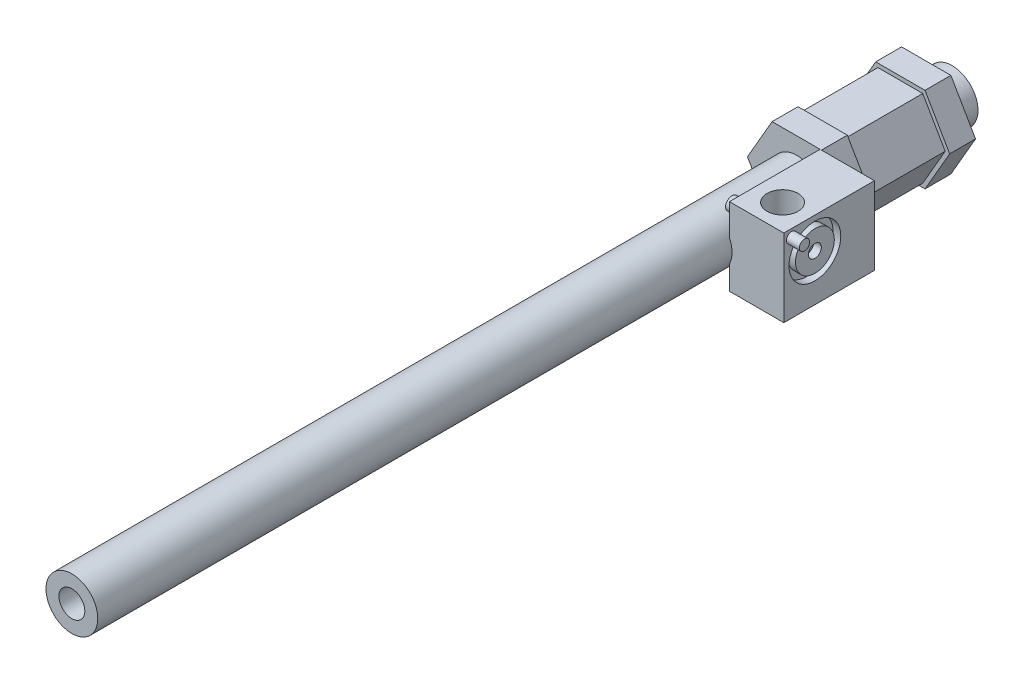
SolidWorks part; units mm, degrees
ref_plane "Front Plane" through (0, 0, 0) normal (0, 0, 1) x (1, 0, 0)
ref_plane "Top Plane" through (0, 0, 0) normal (0, 1, 0) x (1, 0, 0)
ref_plane "Right Plane" through (0, 0, 0) normal (1, 0, 0) x (0, 0, -1)
sketch "Sketch1" plane through (0, 0, 0) normal (0, 0, 1) x (1, 0, 0)
  circle A0 centre (0, 0) radius 10
  dimension "D1" = 20
extrude "Boss-Extrude1" add sketch "Sketch1" along normal blind 340
sketch "Sketch2" plane through (0, 0, 340) normal (0, 0, 1) x (1, 0, 0)
  circle A0 centre (0, 0) radius 5
  dimension "D1" = 10
extrude "Cut-Extrude1" cut sketch "Sketch2" against normal blind 330
sketch "Sketch3" plane through (0, 0, 0) normal (0, 0, -1) x (-1, 0, 0)
  line L1 (17.3205, 0) -> (8.6603, 15)
  line L2 (8.6603, 15) -> (-8.6603, 15)
  line L3 (-8.6603, 15) -> (-17.3205, 0)
  line L4 (-17.3205, 0) -> (-8.6603, -15)
  line L5 (-8.6603, -15) -> (8.6603, -15)
  line L6 (8.6603, -15) -> (17.3205, 0)
  circle A0 centre (0, 0) radius 15 construction
  circle A2 centre (0, 0) radius 10
  circle A3 centre (0, 0) radius 10 construction
  dimension "D1" = 30
extrude "Boss-Extrude2" add sketch "Sketch3" against normal blind 50 from offset 10 offset against normal yes
sketch "Sketch4" plane through (0, 0, 10) normal (0, 0, -1) x (-1, 0, 0)
  line L0 (8.6603, 15) -> (-8.6603, 15) construction
  line L1 (-9.5263, -16.5) -> (9.5263, -16.5)
  line L2 (9.5263, -16.5) -> (19.0526, 0)
  line L3 (19.0526, 0) -> (9.5263, 16.5)
  line L4 (9.5263, 16.5) -> (-9.5263, 16.5)
  line L5 (-9.5263, 16.5) -> (-19.0526, 0)
  line L6 (-19.0526, 0) -> (-9.5263, -16.5)
  line L7 (17.3205, 0) -> (8.6603, 15) construction
  line L8 (8.6603, -15) -> (17.3205, 0) construction
  line L9 (-8.6603, -15) -> (8.6603, -15) construction
  line L10 (-17.3205, 0) -> (-8.6603, -15) construction
  line L11 (-8.6603, 15) -> (-17.3205, 0) construction
  line L12 (8.6603, 15) -> (-8.6603, 15)
  line L13 (17.3205, 0) -> (8.6603, 15)
  line L14 (8.6603, -15) -> (17.3205, 0)
  line L15 (-8.6603, -15) -> (8.6603, -15)
  line L16 (-17.3205, 0) -> (-8.6603, -15)
  line L17 (-8.6603, 15) -> (-17.3205, 0)
  circle A0 centre (0, 0) radius 16.5 construction
  dimension "D1" = 33
extrude "Boss-Extrude3" add sketch "Sketch4" against normal blind 10
extrude "Boss-Extrude4" add sketch "Sketch4<2>" against normal blind 10 from offset 40 offset against normal yes
sketch "Sketch4<2>" plane through (0, 0, 10) normal (0, 0, -1) x (-1, 0, 0) same geometry as "Sketch4"
ref_plane "Plane1" through (10, 0, 0) normal (1, 0, 0) x (0, 0, -1)
sketch "Sketch5" plane through (10, 0, 0) normal (1, 0, 0) x (0, 0, -1)
  line L0 (-60, 16.5) -> (-50, 16.5) construction
  line L1 (-60, 16.5) -> (-95, 16.5)
  line L2 (-60, 16.5) -> (-60, -13.5)
  line L3 (-60, -13.5) -> (-95, -13.5)
  line L4 (-95, 16.5) -> (-95, -13.5)
  line L5 (-60, 10) -> (-60, -10) construction
  dimension "D1" = 35
  dimension "D2" = 30
extrude "Boss-Extrude6" add sketch "Sketch5" along normal blind 10 from offset 10 separate body
sketch "Sketch6" plane through (20, 0, 0) normal (-1, 0, 0) x (0, 0, 1)
  line L4 (60, 16.5) -> (60, -13.5)
  line L5 (60, -13.5) -> (95, -13.5)
  line L6 (95, -13.5) -> (95, 16.5)
  line L7 (95, 16.5) -> (60, 16.5)
  line L8 (60, 16.5) -> (60, -13.5)
  line L9 (60, -13.5) -> (95, -13.5)
  line L10 (95, -13.5) -> (95, 16.5)
  line L11 (95, 16.5) -> (60, 16.5)
  dimension "D1" = 0
extrude "Boss-Extrude8" add sketch "Sketch6" along normal blind 11
sketch "Sketch7" plane through (0, 16.5, 0) normal (0, 1, 0) x (1, 0, 0)
  line L0 (9, -95) -> (30, -95) construction
  circle A0 centre (19.5, -85) radius 6
  point P5 (19.5, -95)
  dimension "D1" = 12
  dimension "D2" = 10
extrude "Cut-Extrude2" cut sketch "Sketch7" against normal blind 21
sketch "Sketch8" plane through (9, 0, 0) normal (-1, 0, 0) x (0, 0, 1)
  line L0 (95, 4.3589) -> (95, 16.5) construction
  line L1 (95, 16.5) -> (60, 16.5) construction
  circle A0 centre (90, 11.5) radius 2.5
  dimension "D1" = 5
  dimension "D2" = 5
  dimension "D3" = 5
extrude "Boss-Extrude9" add sketch "Sketch8" along normal blind 4
sketch "Sketch9" plane through (30, 0, 0) normal (1, 0, 0) x (0, 0, -1)
  line L0 (-60, 16.5) -> (-95, 16.5) construction
  circle A0 centre (-83, 4.5) radius 10
  circle A1 centre (-83, 4.5) radius 7.5
  circle A2 centre (-83, 4.5) radius 2.5
  dimension "D3" = 20
  dimension "D4" = 15
  dimension "D5" = 5
  dimension "D1" = 12
  dimension "D2" = 12
extrude "Cut-Extrude3" cut sketch "Sketch9" against normal blind 3 contours A0 A1 | A2 region at (30, 4.5, 92.7172) region at (30, 4.5, 83)
sketch "Sketch10" plane through (30, 0, 0) normal (1, 0, 0) x (0, 0, -1)
  line L0 (-60, 16.5) -> (-95, 16.5) construction
  line L1 (-95, 16.5) -> (-95, -13.5) construction
  circle A0 centre (-92, 13.5) radius 2
  dimension "D1" = 4
  dimension "D2" = 3
  dimension "D3" = 3
extrude "Boss-Extrude10" add sketch "Sketch10" along normal blind 5
